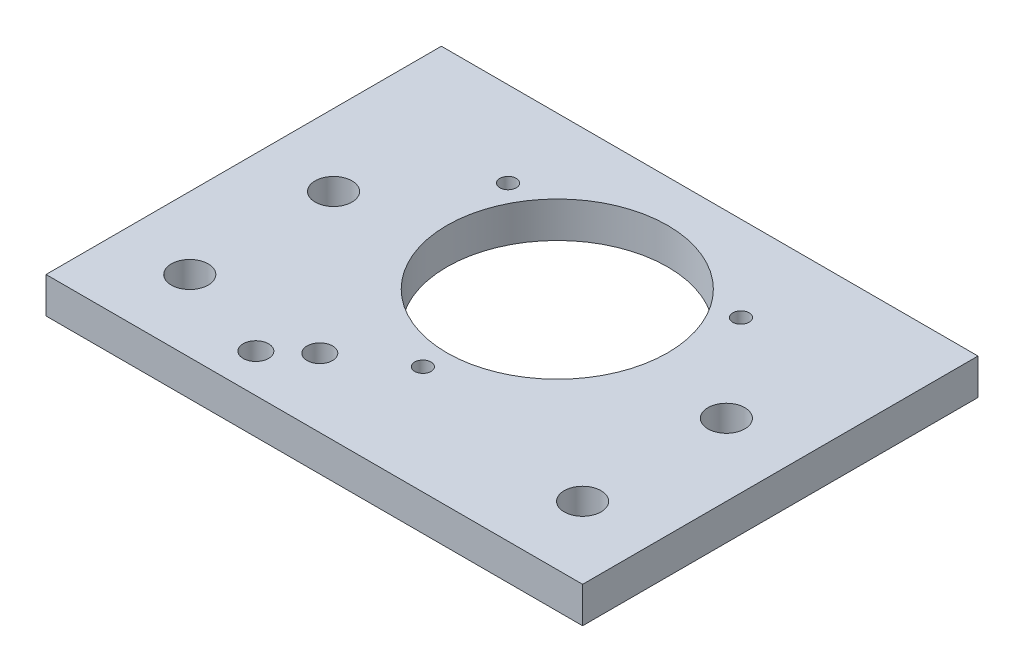
SolidWorks part; units mm, degrees
ref_plane "Front Plane" through (0, 0, 0) normal (0, 0, 1) x (1, 0, 0)
ref_plane "Top Plane" through (0, 0, 0) normal (0, 1, 0) x (1, 0, 0)
ref_plane "Right Plane" through (0, 0, 0) normal (1, 0, 0) x (0, 0, -1)
sketch "Sketch1" plane through (0, 0, 0) normal (0, 1, 0) x (1, 0, 0)
  line L0 (-34.7, 3.175) -> (34.7, 3.175) construction
  line L1 (-47.4, 34.925) -> (47.4, 34.925)
  line L2 (-47.4, 34.925) -> (-47.4, -34.925)
  line L3 (-47.4, -34.925) -> (47.4, -34.925)
  line L4 (47.4, 34.925) -> (47.4, -34.925)
  line L5 (-47.4, 34.925) -> (47.4, -34.925) construction
  line L6 (-47.4, -34.925) -> (47.4, 34.925) construction
  line L7 (22, -34.925) -> (47.4, -34.925) construction
  line L8 (-17.1383, -28.1118) -> (-11.1649, -22.7903) construction
  line L9 (-34.7, -22.225) -> (34.7, -22.225) construction
  line L10 (-34.7, -22.225) -> (-34.7, 22.225) construction
  line L11 (-34.7, 22.225) -> (34.7, 22.225) construction
  line L12 (34.7, -22.225) -> (34.7, 22.225) construction
  line L13 (-34.7, -22.225) -> (34.7, 22.225) construction
  line L14 (-34.7, 22.225) -> (34.7, -22.225) construction
  line L15 (0, 0) -> (0, 8) construction
  line L16 (-19.7991, -25.1251) -> (-13.8257, -19.8036) construction
  line L17 (22, -34.925) -> (22, -9.525) construction
  line L18 (22, -9.525) -> (47.4, -9.525) construction
  line L19 (47.4, -34.925) -> (47.4, -9.525) construction
  line L20 (22, -34.925) -> (47.4, -9.525) construction
  line L21 (22, -9.525) -> (47.4, -34.925) construction
  line L22 (0, 8) -> (0, -15.75) construction
  line L23 (0, 8) -> (20.5681, 19.875) construction
  line L24 (0, 8) -> (-20.5681, 19.875) construction
  line L25 (-14.4776, -31.0985) -> (-8.5042, -25.7771) construction
  line L27 (-47.4, -34.925) -> (-22, -34.925)
  line L28 (-47.4, -34.925) -> (-47.4, -9.525)
  line L29 (-47.4, -9.525) -> (-22, -9.525) construction
  line L30 (-22, -34.925) -> (-22, -9.525) construction
  circle A18 centre (-34.7, 22.225) radius 3.2576 construction
  circle A19 centre (34.7, 22.225) radius 3.2576 construction
  circle A20 centre (34.7, -22.225) radius 3.2576
  circle A21 centre (-34.7, -22.225) radius 3.2576
  circle A22 centre (-11.1649, -22.7903) radius 2.25
  circle A24 centre (0, 8) radius 19.5
  circle A25 centre (0, 8) radius 23.75 construction
  circle A30 centre (-34.7, 3.175) radius 3.2576
  circle A31 centre (34.7, 3.175) radius 3.2576
  circle A32 centre (0, -15.75) radius 1.45
  circle A33 centre (-20.5681, 19.875) radius 1.45
  circle A34 centre (20.5681, 19.875) radius 1.45
  circle A35 centre (0, 8) radius 26.5 construction
  circle A36 centre (-17.1383, -28.1118) radius 2.25
  arc A37 (-19.7991, -25.1251) -> (-14.4776, -31.0985) centre (-17.1383, -28.1118) ccw construction
  arc A38 (-8.5042, -25.7771) -> (-13.8257, -19.8036) centre (-11.1649, -22.7903) ccw construction
  circle A39 centre (-11.1649, -22.7903) radius 6 construction
  point P11 (-14.1516, -25.4511)
  point P51 (0, 34.5)
  dimension "D2" = 8
  dimension "D4" = 39
  dimension "D7" = 47.5
  dimension "D10" = 120
  dimension "D13" = 12.7
  dimension "D15" = 6.5151
  dimension "D16" = 4
  dimension "D17" = 4.5
  dimension "D9" = 120
  dimension "D5" = 8
  dimension "D12" = 2.9
  dimension "D18" = 53
  dimension "D19" = 12
  dimension "D6" = 94.8
  dimension "D8" = 69.85
  dimension "D11" = 25.4
  dimension "D14" = 12.7
  dimension "D3" = 25.4
extrude "Boss-Extrude1" add sketch "Sketch1" along normal blind 6.35 contours L4 L1 L2 L3 A36 A34 A33 A32 A31 A30 A24 A22 A21 A20 region at (0, 0, -33.7475)
sketch "Sketch4" plane through (0, 0, 0) normal (0, -1, 0) x (1, 0, 0)
  line L6 (-17.1383, 28.1118) -> (-11.1649, 22.7903) construction
  line L7 (-14.145, 31.4719) -> (-8.1716, 26.1504)
  line L8 (-20.1317, 24.7518) -> (-14.1582, 19.4303)
  circle A6 centre (-11.1649, 22.7903) radius 2.25 construction
  circle A7 centre (-17.1383, 28.1118) radius 2.25 construction
  circle A8 centre (-11.1649, 22.7903) radius 2.25
  circle A9 centre (-17.1383, 28.1118) radius 2.25
  arc A10 (-14.145, 31.4719) -> (-20.1317, 24.7518) centre (-17.1383, 28.1118) ccw
  arc A11 (-14.1582, 19.4303) -> (-8.1716, 26.1504) centre (-11.1649, 22.7903) ccw
  point P23 (-14.1516, 25.4511)
  dimension "D2" = 4.5
extrude "Cut-Extrude2" cut sketch "Sketch4" against normal blind 3 contours L8 A11 L7 A10 A9 A8 region at (-14.1516, 0, 25.4511)
equation "\"testbed_height\" = 91.50mm"
equation "\"plate_thickness\" = 6mm"
equation "\"main_body_splay_length\" = 48.5mm"
equation "\"splay_shaft_length_no_wires\" = 10mm"
equation "\"splay_shaft_length_wires\" = 6.5mm"
equation "\"timing_pulley_offset\" = 0mm"
equation "\"effective_motor_length\" = \"timing_pulley_offset\" + \"splay_shaft_length_no_wires\" + \"main_body_splay_length\""
equation "\"80_20_side\" = 25.4mm"
equation "\"80_20_length\" = 152.4mm"
equation "\"80_20_optic_mount_length\" = \"80_20_length\" - 25.4mm"
equation "\"optic_board_hole_size\" = 6.35mm"
equation "\"total_mounting_length\" = \"testbed_height\" - \"effective_motor_length\" - \"80_20_side\""
equation "\"mounting_vertical_portion_height\" = \"total_mounting_length\" - 2 * \"plate_thickness\""
equation "\"face_mount_width\" = 15.25mm"
equation "\"center_dist_to_face_mount_vertical_screws\" = 5mm"
equation "\"D1@Boss-Extrude1\"=0.25in"
